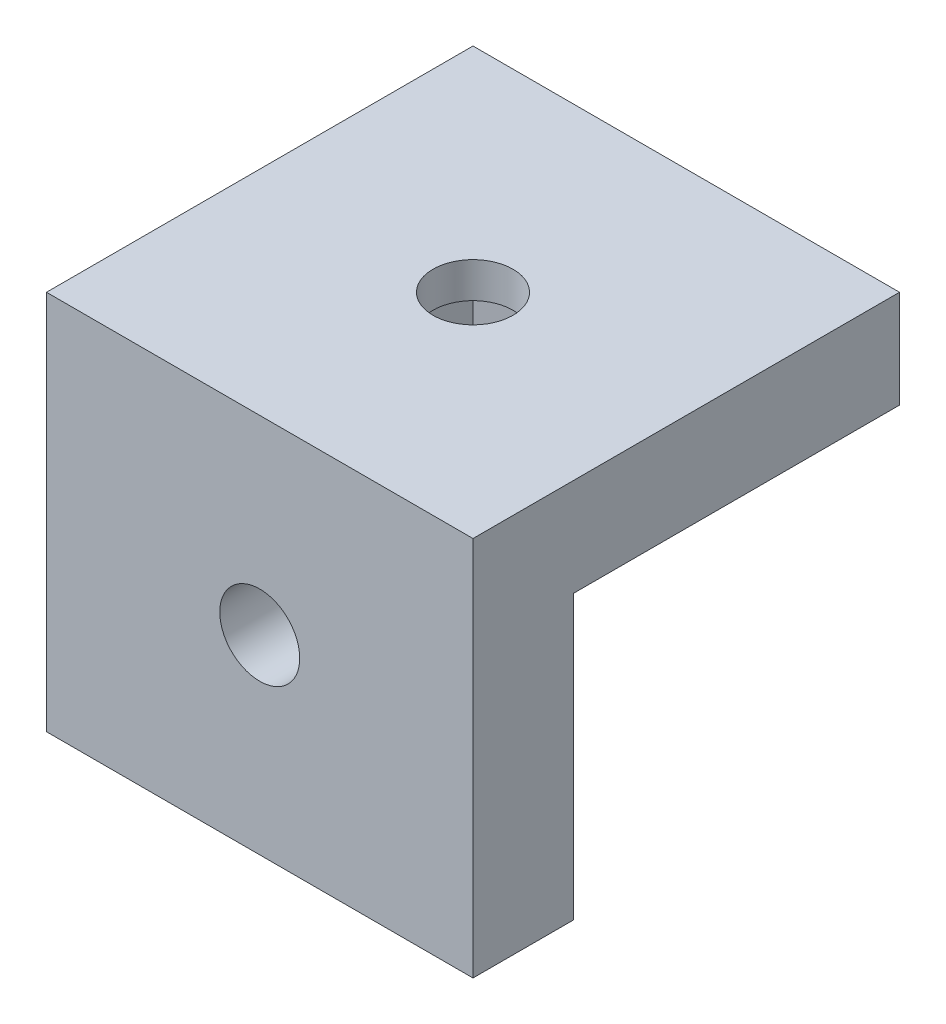
SolidWorks part; units mm, degrees
ref_plane "Front Plane" through (0, 0, 0) normal (0, 0, 1) x (1, 0, 0)
ref_plane "Top Plane" through (0, 0, 0) normal (0, 1, 0) x (1, 0, 0)
ref_plane "Right Plane" through (0, 0, 0) normal (1, 0, 0) x (0, 0, -1)
sketch "Sketch1" plane through (0, 0, 0) normal (0, 1, 0) x (1, 0, 0)
  line L1 (0, 0) -> (38.1, 0)
  line L5 (0, 0) -> (0, 38.1)
  line L6 (0, 38.1) -> (38.1, 38.1)
  line L8 (38.1, 38.1) -> (38.1, 0)
  point P1 (38.1, 37.7355)
  dimension "D1" = 38.1
extrude "Main Body" add sketch "Sketch1" along normal blind 34
sketch "Sketch3" plane through (0, 0, 0) normal (0, 0, 1) x (1, 0, 0)
  line L0 (0, 0) -> (38.1, 34) construction
  circle A0 centre (19.05, 17) radius 3.5719
  circle A1 centre (19.05, 17) radius 7.9375 construction
  dimension "D1" = 7.1437
  dimension "D2" = 15.875
extrude "9/32 Right Rail" cut sketch "Sketch3" against normal blind 5.5562 and the other way through all
sketch "Sketch4" plane through (0, 0, 0) normal (-1, 0, 0) x (0, 0, 1)
  line L0 (0, 0) -> (-38.1, 34) construction
  circle A0 centre (-19.05, 17) radius 3.5719
  circle A1 centre (-19.05, 17) radius 7.9375 construction
  dimension "D1" = 7.1437
  dimension "D2" = 15.875
extrude "9/32 Left Rail" cut sketch "Sketch4" against normal blind 5.5562
sketch "Sketch8" plane through (0, 34, 0) normal (0, 1, 0) x (1, 0, 0)
  line L0 (0, 0) -> (38.1, 38.1) construction
  circle A0 centre (19.05, 19.05) radius 3.175 construction
  circle A1 centre (19.05, 19.05) radius 7.9375 construction
  circle A2 centre (19.05, 19.05) radius 3.5719
  point P3 (23.1695, 22.745)
  point P4 (38.1, 38.1)
  point P15 (23.8125, 23.8125)
  dimension "D1" = 6.35
  dimension "D2" = 15.875
  dimension "D3" = 0.3969
extrude "9/32 Topper" cut sketch "Sketch8" against normal blind 10 and the other way through all
ref_plane "Plane1" through (5.5562, 0, 0) normal (-1, 0, 0) x (0, 0, 1)
sketch "Sketch9" plane through (0, 0, 0) normal (-1, 0, 0) x (0, 0, 1)
  line L0 (-19.05, 0) -> (-19.05, 34) construction
  line L1 (-12.6342, 17) -> (-15.8421, 22.5562) construction
  line L2 (-15.8421, 22.5562) -> (-22.2579, 22.5562) construction
  line L3 (-22.2579, 22.5562) -> (-25.4658, 17) construction
  line L4 (-25.4658, 17) -> (-22.2579, 11.4437) construction
  line L5 (-22.2579, 11.4437) -> (-15.8421, 11.4437) construction
  line L6 (-15.8421, 11.4437) -> (-12.6342, 17) construction
  line L7 (-38.1, 0) -> (0, 0) construction
  line L8 (-38.1, 34) -> (0, 34) construction
  line L9 (-22.3725, 22.7547) -> (-25.6949, 17)
  line L10 (-25.6949, 17) -> (-22.3725, 11.2453)
  line L11 (-22.3725, 11.2453) -> (-15.7275, 11.2453)
  line L12 (-15.7275, 11.2453) -> (-12.4051, 17)
  line L13 (-12.4051, 17) -> (-15.7275, 22.7547)
  line L14 (-15.7275, 22.7547) -> (-22.3725, 22.7547)
  line L15 (-38.1, 27.65) -> (-38.1, 6.35) construction
  line L16 (-38.1, 34) -> (-38.1, 0) construction
  line L17 (-38.1, 6.35) -> (-5.5562, 6.35) construction
  line L18 (-5.5562, 6.35) -> (-5.5562, 27.65) construction
  line L19 (-5.5562, 27.65) -> (-38.1, 27.65) construction
  line L20 (0, 34) -> (0, 0) construction
  circle A0 centre (-19.05, 17) radius 5.5563 construction
  point P15 (-19.05, 17)
  point P27 (-38.1, 17)
  point P29 (-38.1, 17)
  dimension "D1" = 11.1125
  dimension "D3" = 5.5562
  dimension "D4" = 6.35
  dimension "D2" = 0.1984
extrude "Cut-Extrude3" cut sketch "Sketch9" against normal up to surface (38.1 mm away) from surface up to face at (38.1, 17, -19.05) starting at plane "Plane1"
ref_plane "Plane2" through (0, 0, -5.5563) normal (0, 0, 1) x (1, 0, 0)
sketch "Sketch10" plane through (0, 0, 0) normal (0, 0, 1) x (1, 0, 0)
  line L0 (19.05, 0) -> (19.05, 34) construction
  line L1 (0, 0) -> (38.1, 0) construction
  line L2 (0, 34) -> (38.1, 34) construction
  line L3 (15.7275, 22.7547) -> (12.4051, 17)
  line L4 (25.4658, 17) -> (22.2579, 22.5562) construction
  line L5 (22.2579, 22.5562) -> (15.8421, 22.5562) construction
  line L6 (15.8421, 22.5562) -> (12.6342, 17) construction
  line L13 (12.6342, 17) -> (15.8421, 11.4437) construction
  line L14 (15.8421, 11.4437) -> (22.2579, 11.4437) construction
  line L15 (22.2579, 11.4437) -> (25.4658, 17) construction
  line L16 (12.4051, 17) -> (15.7275, 11.2453)
  line L17 (15.7275, 11.2453) -> (22.3725, 11.2453)
  line L18 (22.3725, 11.2453) -> (25.6949, 17)
  line L19 (25.6949, 17) -> (22.3725, 22.7547)
  line L20 (22.3725, 22.7547) -> (15.7275, 22.7547)
  circle A0 centre (19.05, 17) radius 5.5563 construction
  dimension "D1" = 11.1125
  dimension "D2" = 0.1984
extrude "Cut-Extrude4" cut sketch "Sketch10" against normal up to surface (38.1 mm away) from surface up to face at (19.05, 17, -38.1) starting at plane "Plane2"
sketch "Sketch13" plane through (0, 34, 0) normal (0, 1, 0) x (1, 0, 0)
  line L2 (38.1, 8.9807) -> (8.9807, 8.9807)
  line L3 (8.9807, 38.1) -> (8.9807, 8.9807)
  line L7 (38.1, 38.1) -> (0, 38.1) construction
  line L8 (38.1, 0) -> (38.1, 38.1) construction
  line L9 (8.9807, 38.1) -> (38.1, 38.1)
  line L10 (38.1, 38.1) -> (38.1, 8.9807)
  line L11 (12.4051, 12.4051) -> (12.4051, 5.5563) construction
  line L12 (12.4051, 12.4051) -> (5.5562, 12.4051) construction
  line L13 (12.4051, 12.4051) -> (12.4051, 5.5563) construction
  line L14 (12.4051, 12.4051) -> (5.5562, 12.4051) construction
  point P2 (11.9062, 10.933)
  point P3 (7.0767, 7.0767)
  point P5 (8.1046, 8.1046)
  point P10 (12.4051, 8.9807)
ref_plane "Plane4" through (0, 17, 0) normal (0, 1, 0) x (1, 0, 0)
extrude "Cut-Extrude12" cut sketch "Sketch13" along direction (0, -1, 0) on the side of the normal offset from surface 8.7312 and the other way offset from surface 3.175 from surface up to face at (19.05, 34, -22.6219) other way up to face at (19.05, 0, -19.05) starting at plane "Plane4"
sketch "Sketch14" plane through (0, 34, 0) normal (0, 1, 0) x (1, 0, 0)
  line L0 (38.1, 0) -> (0, 38.1) construction
  line L1 (23.7487, 14.3513) -> (25.4685, 20.7698)
  line L2 (23.5867, 14.5133) -> (25.2472, 20.7105) construction
  line L3 (25.2472, 20.7105) -> (20.7105, 25.2472) construction
  line L4 (20.7105, 25.2472) -> (14.5133, 23.5867) construction
  line L5 (14.5133, 23.5867) -> (12.8528, 17.3895) construction
  line L6 (12.8528, 17.3895) -> (17.3895, 12.8528) construction
  line L7 (17.3895, 12.8528) -> (23.5867, 14.5133) construction
  line L8 (25.4685, 20.7698) -> (20.7698, 25.4685)
  line L9 (20.7698, 25.4685) -> (14.3513, 23.7487)
  line L10 (14.3513, 23.7487) -> (12.6315, 17.3302)
  line L11 (12.6315, 17.3302) -> (17.3302, 12.6315)
  line L12 (17.3302, 12.6315) -> (23.7487, 14.3513)
  circle A0 centre (19.05, 19.05) radius 5.5562 construction
  dimension "D1" = 11.1125
  dimension "D2" = 0.1984
extrude "Cut-Extrude15" cut sketch "Sketch14" along normal offset from surface (13.825 mm away) 3.175 from surface up to face at (19.05, 34, -22.6219) starting at plane "Plane4"
sketch "Sketch15" plane through (0, 0, 0) normal (0, -1, 0) x (1, 0, 0)
  line L0 (38.1, -8.9807) -> (8.9807, -38.1)
  line L4 (38.1, -38.1) -> (38.1, -8.9807)
  line L5 (8.9807, -38.1) -> (38.1, -38.1)
  line L6 (8.9807, -8.9807) -> (8.9807, -38.1)
  line L7 (38.1, -8.9807) -> (8.9807, -8.9807)
  line L8 (38.1, -38.1) -> (38.1, -8.9807)
  line L9 (8.9807, -38.1) -> (38.1, -38.1)
  line L10 (8.9807, -8.9807) -> (8.9807, -38.1) construction
  line L11 (38.1, -8.9807) -> (8.9807, -8.9807) construction
  dimension "D1" = 0
extrude "Cut-Extrude16" cut sketch "Sketch15" against normal up to next
